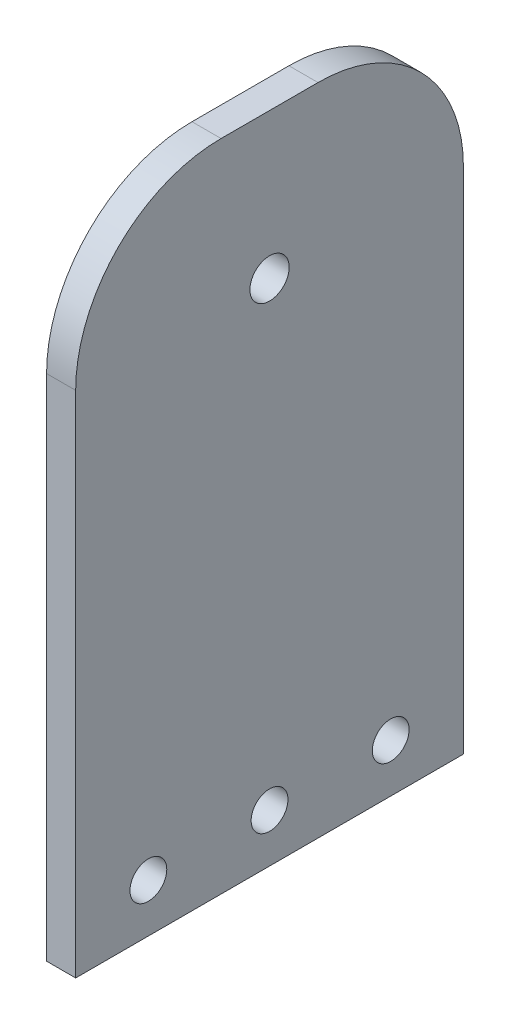
SolidWorks part; units mm, degrees
ref_plane "Front Plane" through (0, 0, 0) normal (0, 0, 1) x (1, 0, 0)
ref_plane "Top Plane" through (0, 0, 0) normal (0, 1, 0) x (1, 0, 0)
ref_plane "Right Plane" through (0, 0, 0) normal (1, 0, 0) x (0, 0, -1)
sketch "Sketch1" plane through (0, 0, 0) normal (1, 0, 0) x (0, 0, -1)
  line L1 (0, 0) -> (40, 0)
  line L2 (0, 0) -> (0, 52.5)
  line L3 (15, 67.5) -> (25, 67.5)
  line L4 (40, 0) -> (40, 52.5)
  arc A1 (25, 67.5) -> (40, 52.5) centre (25, 52.5) cw
  arc A2 (0, 52.5) -> (15, 67.5) centre (15, 52.5) cw
  point P7 (40, 67.5)
  point P10 (0, 67.5)
  dimension "D3" = 15
  dimension "D1" = 40
  dimension "D2" = 52.5
extrude "Boss-Extrude1" add sketch "Sketch1" along normal blind 3 contours L2 L1 L4 region at (0, 32.6224, -20)
ref_axis "Axis1" through (3, 67.5, -20) along (0, -1, 0)
ref_plane "Plane1" through (0, 0, -20) normal (0, 0, -1) x (-1, 0, 0)
hole_wizard "#6 Clearance Hole2" positions "Sketch6" profile "Sketch7" hole size "#6" standard "ANSI Inch" end condition through all
sketch "Sketch6" plane through (3, 0, 0) normal (1, 0, 0) x (0, 0, -1)
  line L0 (0, 0) -> (40, 0) construction
  line L1 (20, -49.3392) -> (20, 49.3392) construction
  point P0 (7.5, 5)
  point P2 (20, 5)
  point P8 (20, 0)
  point P11 (32.5, 5)
  dimension "D1" = 12.5
  dimension "D2" = 5
sketch "Sketch7" plane through (3, 5, -7.5) normal (0, 1, 0) x (0, 0, -1)
  line L0 (0, 0) -> (0, 3)
  line L1 (0, 3) -> (1.8986, 3)
  line L2 (1.8986, 3) -> (1.8986, 0)
  line L5 (1.8986, 0) -> (0, 0)
  line L11 (0, -6.35) -> (0, 107.95) construction
  dimension "Thru Hole Dia." = 3.7973
  dimension "Thru Hole Depth" = 3
sketch "Sketch10" plane through (3, 0, 0) normal (1, 0, 0) x (0, 0, -1)
  line L0 (0, 0) -> (40, 0) construction
  line L1 (20, 67.5) -> (20, -0.1097) construction
  circle A0 centre (20, 52.5) radius 2.025
  dimension "D2" = 4.05
  dimension "D1" = 52.5
extrude "Cut-Extrude1" cut sketch "Sketch10" against normal blind 10
equation "\"Shaft Height\"= 52.5mm"
equation "\"D2@Sketch1\"=\"Shaft Height\""
equation "\"D1@Sketch10\"=\"Shaft Height\""
